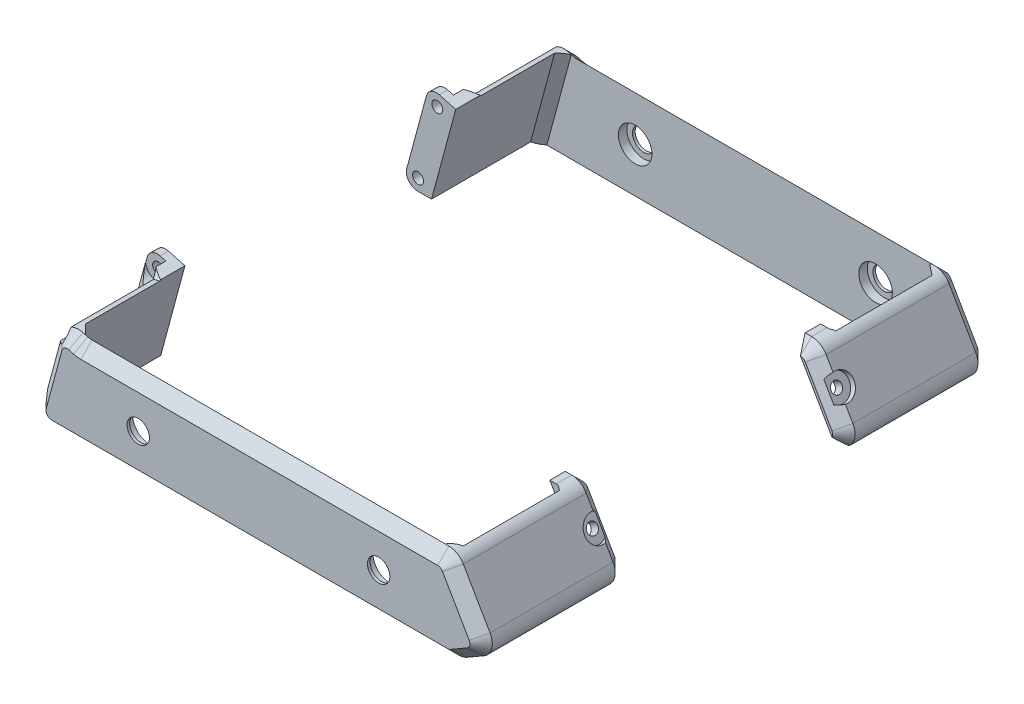
SolidWorks part; units mm, degrees
material "PE High Density"
ref_plane "Front Plane" through (0, 0, 0) normal (0, 0, 1) x (1, 0, 0)
ref_plane "Top Plane" through (0, 0, 0) normal (0, 1, 0) x (1, 0, 0)
ref_plane "Right Plane" through (0, 0, 0) normal (1, 0, 0) x (0, 0, -1)
sketch "Sketch1" plane through (0, 0, 0) normal (0, 0, 1) x (1, 0, 0)
  line L0 (104.7291, 16) -> (-21.2959, 16) construction
  line L1 (-21.2959, 16) -> (104.7291, 16)
  line L2 (-21.2959, 16) -> (-21.2959, -16) construction
  line L3 (-21.2959, -16) -> (104.7291, -16)
  line L4 (104.7291, 16) -> (104.7291, -16) construction
  line L5 (120.4547, -11.2375) -> (104.7291, 16) construction
  line L6 (104.7291, 16) -> (120.4547, -11.2375)
  line L7 (120.4547, -11.2375) -> (112.2058, -16)
  line L8 (112.2058, -16) -> (104.7291, -16)
  line L9 (-21.2959, 16) -> (-29.5825, 18.2352)
  line L10 (-21.2959, 16) -> (-29.5825, 18.2352) construction
  line L11 (-29.5825, 18.2352) -> (-38.8169, -16)
  line L12 (-40.9357, -16) -> (112.2058, -16) construction
  line L13 (-38.8169, -16) -> (-21.2959, -16)
extrude "Boss-Extrude1" add sketch "Sketch1" against normal blind 4 from offset 0.95
sketch "Sketch2" plane through (0, 0, 0.95) normal (0, 0, 1) x (1, 0, 0)
  line L0 (104.7291, 16) -> (110.5026, 16)
  line L1 (110.5026, 16) -> (124.7848, -8.7375)
  line L2 (124.7848, -8.7375) -> (120.4547, -11.2375)
  line L3 (112.2058, -16) -> (120.4547, -11.2375) construction
  line L4 (120.4547, -11.2375) -> (104.7291, 16) construction
  line L5 (120.4547, -11.2375) -> (104.7291, 16)
  dimension "D1" = 5
extrude "Boss-Extrude2" add sketch "Sketch2" against normal up to surface (51.95 mm away)
sketch "Sketch8" plane through (0, 0, -3.05) normal (0, 0, -1) x (-1, 0, 0)
  line L0 (21.2959, 16) -> (29.5825, 18.2352) construction
  line L1 (29.5825, 18.2352) -> (38.8169, -16) construction
  line L2 (25.7205, 17.1935) -> (29.5825, 18.2352)
  line L3 (29.5825, 18.2352) -> (38.8169, -16)
  line L5 (38.8169, -16) -> (-112.2058, -16) construction
  line L6 (34.6739, -16) -> (38.8169, -16)
  line L7 (25.7205, 17.1935) -> (34.6739, -16)
  point P6 (33.0293, -16)
  dimension "D1" = 4
extrude "Boss-Extrude3" add sketch "Sketch8" along normal up to surface (38.425 mm away)
sketch "Sketch3" plane through (0, 0, -3.05) normal (0, 0, -1) x (-1, 0, 0)
  circle A0 centre (-85.9583, 0) radius 25 construction
  circle A1 centre (-85.9583, 0) radius 25 construction
  arc A2 (-111.1191, -12.2855) -> (-113.3014, 6.0295) centre (-85.9583, 0) ccw
  circle A3 centre (0, 0) radius 25 construction
  circle A4 centre (0, 0) radius 25 construction
  circle A5 centre (0, 0) radius 28
  arc A8 (-116.9817, -1.8606) -> (-111.1191, -12.2855) centre (-111.8303, -5.8245) ccw
  arc A10 (-113.3014, 6.0295) -> (-116.9817, -1.8606) centre (-132.8321, 10.3363) cw
  circle A11 centre (-85.9583, 0) radius 28 construction
  circle A12 centre (-111.8303, -5.8245) radius 5.25 construction
  point P13 (-57.9583, 0)
  dimension "D2" = 20
  dimension "D3" = 6.5
  dimension "D1" = 3
extrude "Cut-Extrude1" cut sketch "Sketch3" along normal up to surface (38.425 mm away)
fillet "Fillet2" radius 6 6 edges at (124.7848, -8.7375, -25.025) (110.5026, 16, -25.025) (112.2058, -16, -1.05) (-21.2959, 16, -1.05) (-38.8169, -16, -20.2625) (-29.5825, 18.2352, -20.2625)
fillet "Fillet3" [suppressed] radius 1
sketch "Sketch4" plane through (0, 0, 0.95) normal (0, 0, 1) x (1, 0, 0)
  circle A0 centre (0, 0) radius 4 construction
  circle A1 centre (0, 0) radius 4
  circle A2 centre (85.9583, 0) radius 4 construction
  circle A3 centre (85.9583, 0) radius 4
extrude "Cut-Extrude2" cut sketch "Sketch4" against normal through all
sketch "Sketch5" plane through (0, 0, 0.95) normal (0, 0, 1) x (1, 0, 0)
  circle A0 centre (0, 0) radius 6
  circle A1 centre (85.9583, 0) radius 6
  dimension "D1" = 12
extrude "Cut-Extrude4" cut sketch "Sketch5" against normal up to surface (6 mm away) from surface at -0.95
chamfer "Chamfer1" distance 4 angle 45 23 edges at (-22.0634, 16.207, -1.05) (-23.7895, 16.6726, -1.05) (-20.5009, 16, -1.05) (119.5887, -11.7375, -1.05) (113.5981, -15.1962, -1.05) (117.0098, 4.7293, -51) (110.0385, 15.1962, -51) (122.4938, -7.6042, -51) (-21.289, 16.052, 0.95) (105.8838, 16, -51) (-33.961, 2.0024, 0.95) (-22.9265, 16.4398, 0.95) (39.807, -16, 0.95) (116.5934, -13.4668, 0.95) (117.0098, 4.7293, 0.95) (43.2688, 16, 0.95) (110.0385, 15.1962, 0.95) (122.3842, -8.0943, 0.95) (112.151, -15.7956, 0.95) (-28.3434, 16.0808, 0.95) (-35.7472, -13.6486, 0.95) (110.5981, -16, -1.05) (-30.984, -16, -1.05)
sketch "Sketch6" plane through (85.475, 49.349, 0) normal (-0.866, -0.5, 0) x (0, 0, 1)
  line L0 (-41.475, -57.8593) -> (-51, -57.8593) construction
  line L1 (-51, -50.6082) -> (-41.475, -50.6082) construction
  line L2 (-41.475, -57.8593) -> (-51, -57.8593) construction
  line L3 (-51, -50.6082) -> (-41.475, -50.6082) construction
  line L4 (-46.2375, -57.8593) -> (-46.2375, -50.6082) construction
  circle A0 centre (-46.2375, -54.2337) radius 1.95
  dimension "D1" = 3.9
extrude "Cut-Extrude5" cut sketch "Sketch6" against normal through all
sketch "Sketch7" plane through (85.475, 49.349, 0) normal (-0.866, -0.5, 0) x (0, 0, 1)
  circle A0 centre (-46.2375, -54.2337) radius 4.5
  circle A1 centre (-46.2375, -54.2337) radius 1.95 construction
  dimension "D1" = 9
extrude "Cut-Extrude6" cut sketch "Sketch7" against normal through all from offset 3 offset against normal yes
ref_plane "Plane1" through (0, 0, -89.8875) normal (0, 0, 1) x (1, 0, 0)
sketch "Sketch9" plane through (0, 0, -41.475) normal (0, 0, -1) x (-1, 0, 0)
  line L3 (31.822, 16.5721) -> (31.2519, 18.6855) construction
  line L4 (25.7205, 17.1935) -> (31.6274, 18.7868)
  line L5 (34.3882, -14.9408) -> (39.387, -14.9408)
  line L6 (36.2246, 16.1428) -> (43.249, -9.8991)
  line L7 (36.3259, 15.7672) -> (34.2125, 15.1972) construction
  line L8 (21.2959, 16) -> (29.5825, 18.2352) construction
  line L9 (39.2056, -12.7519) -> (39.2056, -14.9408) construction
  line L10 (41.0884, -10.294) -> (43.2018, -9.724) construction
  line L11 (32.604, 15.1662) -> (32.3298, 14.6894) construction
  line L12 (39.387, -10.9408) -> (39.2056, -10.8019) construction
  line L13 (34.3882, -14.9408) -> (25.8099, 16.8622) construction
  line L14 (36.777, -8.4374) -> (31.145, 12.4422) construction
  line L15 (34.3882, -14.9408) -> (25.8099, 16.8622)
  line L16 (25.8099, 16.8622) -> (25.7205, 17.1935)
  arc A8 (45.8685, 22.6281) -> (39.6065, 8.3483) centre (48.4727, 12.9731) ccw construction
  arc A9 (39.387, -14.9408) -> (43.249, -9.8991) centre (39.387, -10.9408) ccw
  arc A10 (31.6274, 18.7868) -> (36.2246, 16.1428) centre (32.604, 15.1662) cw
  circle A11 centre (39.2056, -10.8019) radius 1.95
  circle A13 centre (32.3298, 14.6894) radius 1.95
  arc A14 (31.145, 12.4422) -> (25.8099, 16.8622) centre (25.3521, 10.8797) ccw construction
  point P0 (0, 0)
  dimension "D1" = 11
  dimension "D2" = 3.9
  dimension "D3" = 3.75
  dimension "D4" = 4
extrude "Boss-Extrude4" add sketch "Sketch9" against normal blind 3
chamfer "Chamfer2" distance 6 angle 45 4 edges at (-30.9205, 13.1141, -38.475) (-28.6086, 15.919, -38.475) (-36.6161, -12.0687, -38.475) (-33.961, 2.0024, -38.475)
sketch "Sketch11" plane through (0, 0, -41.475) normal (0, 0, -1) x (-1, 0, 0)
  circle A0 centre (32.3298, 14.6894) radius 4.5
  circle A1 centre (39.2056, -10.8019) radius 4.5
  dimension "D1" = 9
extrude "Cut-Extrude7" cut sketch "Sketch11" against normal through all from offset 3 offset against normal yes
chamfer "Chamfer3" distance 3 angle 45 3 edges at (111.7064, 11.0015, -3.05) (114.707, 1.8818, -3.05) (-30.099, 0.9607, -3.05)
fillet "Chamfer4" radius 1 3 edges at (118.18, -4.4348, -41.475) (114.707, 1.8818, -41.475) (111.7064, 11.0015, -41.475) profile chamfer
mirror "Mirror2" about plane through (0, 0, -89.8875) normal (0, 0, 1) of bodies 111 107
